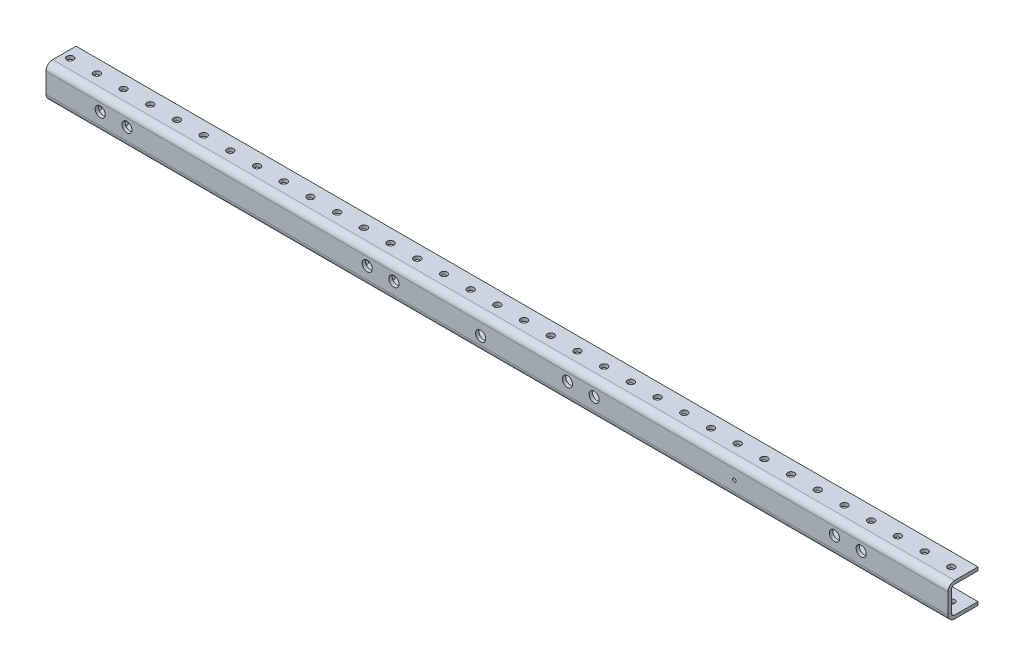
SolidWorks part; units mm, degrees
material "5052-O, Rod (SS)"
ref_plane "Front Plane" through (0, 0, 0) normal (0, 0, 1) x (1, 0, 0)
ref_plane "Top Plane" through (0, 0, 0) normal (0, 1, 0) x (1, 0, 0)
ref_plane "Right Plane" through (0, 0, 0) normal (1, 0, 0) x (0, 0, -1)
ref_plane "Plane1" through (0, 0, 3.175) normal (0, 0, 1) x (1, 0, 0)
sketch "Sketch1" plane through (0, 0, 3.175) normal (0, 0, 1) x (1, 0, 0)
  line L0 (872.98, -7.202) -> (872.98, 24.548)
  line L1 (872.98, 24.548) -> (-16.02, 24.548)
  line L2 (-16.02, 24.548) -> (-16.02, -7.202)
  line L3 (-16.02, -7.202) -> (872.98, -7.202)
extrude "Extrude1" add sketch "Sketch1" against normal blind 28.575
sketch "Sketch2" plane through (-16.02, 0, 0) normal (-1, 0, 0) x (0, 0, 1)
  line L0 (-25.4, 21.373) -> (-25.4, -4.027)
  line L1 (-25.4, -4.027) -> (0, -4.027)
  line L2 (0, -4.027) -> (0, 21.373)
  line L3 (0, 21.373) -> (-25.4, 21.373)
extrude "Extrude2" cut sketch "Sketch2" against normal up to next
hole_wizard "Hole1" positions "Sketch4" profile "Sketch3" legacy
sketch "Sketch4" plane through (0, 24.548, 0) normal (0, 1, 0) x (-1, 0, 0)
  point P0 (3.32, -12.7)
sketch "Sketch3" plane through (-3.32, 24.548, -12.7) normal (1, 0, 0) x (0, 0, 1)
  line L0 (0, 0) -> (0, 3.175)
  line L1 (0, 3.175) -> (3.175, 3.175)
  line L2 (3.175, 3.175) -> (3.175, 0)
  line L3 (3.175, 0) -> (0, 0)
  line L4 (0, 110) -> (0, -10) construction
  dimension "Diameter" = 6.35
  dimension "Depth" = 3.175
sketch3d "3DSketch1"
  point P0 (428.6664, 8.6668, -7.2024)
  point P1 (528.6664, 8.6668, -7.2024)
ref_axis "Axis1" through (528.6664, 8.6668, -7.2024) along (-1, 0, 0)
pattern_linear "LPattern1" count 35 spacing 25.4 along (1, 0, 0) of "Hole1"
hole_wizard "Hole2" positions "Sketch6" profile "Sketch5" legacy
sketch "Sketch6" plane through (0, 0, 3.175) normal (0, 0, 1) x (1, 0, 0)
  point P0 (66.53, 10.578)
sketch "Sketch5" plane through (66.53, 10.578, 3.175) normal (1, 0, 0) x (0, -1, 0)
  line L0 (0, 0) -> (0, 3.175)
  line L1 (0, 3.175) -> (4.826, 3.175)
  line L2 (4.826, 3.175) -> (4.826, 0)
  line L3 (4.826, 0) -> (0, 0)
  line L4 (0, 110) -> (0, -10) construction
  dimension "Diameter" = 9.652
  dimension "Depth" = 3.175
sketch3d "3DSketch2"
  point P0 (428.8468, 8.4517, -7.1294)
  point P1 (528.8468, 8.4517, -7.1294)
ref_axis "Axis2" through (528.8468, 8.4517, -7.1294) along (-1, 0, 0)
pattern_linear "LPattern2" count 12 spacing 25.4 along (1, 0, 0) skipping (2, 0), (3, 0), (4, 0), (5, 0), (6, 0), (7, 0), (8, 0), (9, 0) of "Hole2"
hole_wizard "Hole3" positions "Sketch8" profile "Sketch7" legacy
sketch "Sketch8" plane through (0, 0, 3.175) normal (0, 0, 1) x (1, 0, 0)
  point P0 (428.48, 6.768)
sketch "Sketch7" plane through (428.48, 6.768, 3.175) normal (1, 0, 0) x (0, -1, 0)
  line L0 (0, 0) -> (0, 3.175)
  line L1 (0, 3.175) -> (4.826, 3.175)
  line L2 (4.826, 3.175) -> (4.826, 0)
  line L3 (4.826, 0) -> (0, 0)
  line L4 (0, 110) -> (0, -10) construction
  dimension "Diameter" = 9.652
  dimension "Depth" = 3.175
hole_wizard "Hole4" positions "Sketch10" profile "Sketch9" legacy
sketch "Sketch10" plane through (0, 0, 3.175) normal (0, 0, 1) x (1, 0, 0)
  point P0 (511.03, 10.578)
sketch "Sketch9" plane through (511.03, 10.578, 3.175) normal (1, 0, 0) x (0, -1, 0)
  line L0 (0, 0) -> (0, 3.175)
  line L1 (0, 3.175) -> (4.826, 3.175)
  line L2 (4.826, 3.175) -> (4.826, 0)
  line L3 (4.826, 0) -> (0, 0)
  line L4 (0, 110) -> (0, -10) construction
  dimension "Diameter" = 9.652
  dimension "Depth" = 3.175
sketch3d "3DSketch3"
  point P0 (429.3014, 8.4448, -7.1738)
  point P1 (529.3014, 8.4448, -7.1738)
ref_axis "Axis3" through (529.3014, 8.4448, -7.1738) along (-1, 0, 0)
pattern_linear "LPattern3" count 12 spacing 25.4 along (1, 0, 0) skipping (2, 0), (3, 0), (4, 0), (5, 0), (6, 0), (7, 0), (8, 0), (9, 0) of "Hole4"
hole_wizard "Hole5" positions "Sketch12" profile "Sketch11" legacy
sketch "Sketch12" plane through (0, 0, 3.175) normal (0, 0, 1) x (1, 0, 0)
  point P0 (669.78, 8.673)
sketch "Sketch11" plane through (669.78, 8.673, 3.175) normal (1, 0, 0) x (0, -1, 0)
  line L0 (0, 0) -> (0, 3.175)
  line L1 (0, 3.175) -> (1.5875, 3.175)
  line L2 (1.5875, 3.175) -> (1.5875, 0)
  line L3 (1.5875, 0) -> (0, 0)
  line L4 (0, 110) -> (0, -10) construction
  dimension "Diameter" = 3.175
  dimension "Depth" = 3.175
hole_wizard "Hole6" positions "Sketch14" profile "Sketch13" legacy
sketch "Sketch14" plane through (0, -4.027, 0) normal (0, 1, 0) x (-1, 0, 0)
  point P0 (3.32, -12.7)
sketch "Sketch13" plane through (-3.32, -4.027, -12.7) normal (1, 0, 0) x (0, 0, 1)
  line L0 (0, 0) -> (0, 3.175)
  line L1 (0, 3.175) -> (3.175, 3.175)
  line L2 (3.175, 3.175) -> (3.175, 0)
  line L3 (3.175, 0) -> (0, 0)
  line L4 (0, 110) -> (0, -10) construction
  dimension "Diameter" = 6.35
  dimension "Depth" = 3.175
sketch3d "3DSketch4"
  point P0 (428.6444, 8.4444, -7.1991)
  point P1 (528.6444, 8.4444, -7.1991)
ref_axis "Axis4" through (528.6444, 8.4444, -7.1991) along (-1, 0, 0)
pattern_linear "LPattern4" count 35 spacing 25.4 along (1, 0, 0) of "Hole6"
fillet "Fillet1" radius 3.175 1 edges at (428.48, 21.373, 0) tangent propagation no
fillet "Fillet2" radius 3.175 1 edges at (428.48, -4.027, 0) tangent propagation no
fillet "Fillet3" radius 6.35 1 edges at (428.48, -7.202, 3.175) tangent propagation no
fillet "Fillet4" radius 6.35 1 edges at (428.48, 24.548, 3.175) tangent propagation no
ref_plane "Plane2" through (872.98, 24.548, -3.175) normal (1, 0, 0) x (0, 0, -1)
sketch "Sketch16" plane through (0, 24.548, 0) normal (0, 1, 0) x (1, 0, 0)
  line L0 (14.98, 3.175) -> (14.98, 25.4) construction
  line L1 (-16.02, 3.175) -> (872.98, 3.175) construction
  line L2 (872.98, 25.4) -> (-16.02, 25.4) construction
  line L3 (872.98, 25.4) -> (872.98, 3.175) construction
  line L6 (14.98, 3.175) -> (14.98, 25.4)
  line L7 (14.98, 25.4) -> (-16.02, 25.4)
  line L9 (14.98, 25.4) -> (-32.7801, 25.4)
  line L10 (14.98, 25.4) -> (14.98, -46.1048)
  line L11 (14.98, -46.1048) -> (-32.7801, -46.1048)
  line L12 (-32.7801, 25.4) -> (-32.7801, -46.1048)
  circle M7 centre (-3.32, 12.7) radius 3.175
  line M8 (-16.02, 25.4) -> (-16.02, 3.175)
  line M9 (-16.02, 3.175) -> (872.98, 3.175)
  line M11 (872.98, 25.4) -> (-16.02, 25.4)
  dimension "D1" = 858
extrude "Cut-Extrude2" cut sketch "Sketch16" against normal blind 55 contours L9 L12 L11 L10 M9 M8 | M7 | L6 M9 M11 M8 M7 region at (-0.3851, 24.548, -14.364) region at (-11.0179, 24.548, 16.5797) region at (-3.32, 24.548, -12.7)
